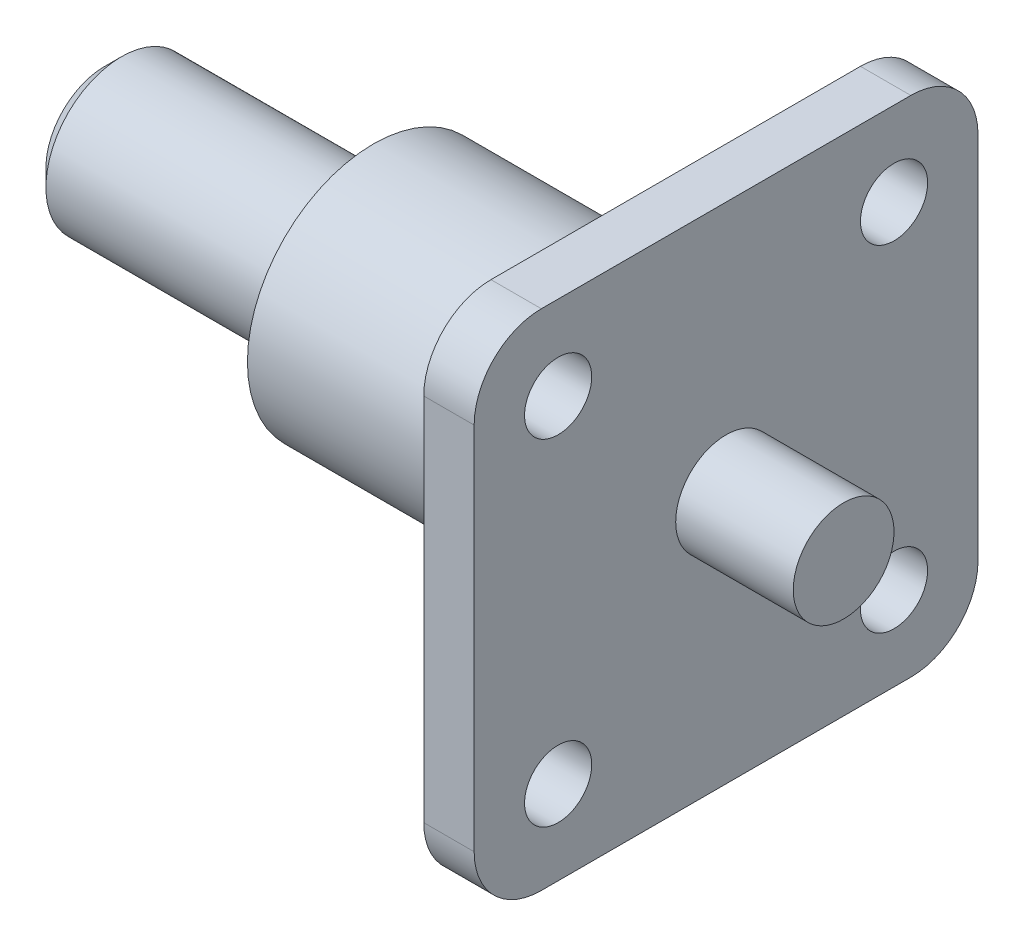
SolidWorks part; units mm, degrees
ref_plane "Alzado" through (0, 0, 0) normal (0, 0, 1) x (1, 0, 0)
ref_plane "Planta" through (0, 0, 0) normal (0, 1, 0) x (1, 0, 0)
ref_plane "Vista lateral" through (0, 0, 0) normal (1, 0, 0) x (0, 0, -1)
sketch "Croquis1" plane through (0, 0, 0) normal (0, 0, 1) x (1, 0, 0)
  line L0 (-18.3711, 0) -> (42.3295, 0) construction
  line L1 (-16, 0) -> (-16, 4.5)
  line L2 (-16, 4.5) -> (0, 4.5)
  line L3 (0, 4.5) -> (0, 7.5)
  line L4 (0, 7.5) -> (18, 7.5)
  line L5 (18, 7.5) -> (18, 0) construction
  line L6 (-16, 0) -> (28, 0)
  line L7 (18, 7.5) -> (18, 3)
  line L8 (18, 3) -> (28, 3)
  line L9 (28, 3) -> (28, 0)
  line L10 (0, 0) -> (0, 8.1876) construction
  point P9 (0, 6)
  point P10 (0, 8.1876)
  dimension "D1" = 9
  dimension "D2" = 15
  dimension "D3" = 16
  dimension "D4" = 18
  dimension "D5" = 6
  dimension "D6" = 10
revolve "Revolución1" add sketch "Croquis1" angle 360 about L0
fillet "Redondeo1" radius 1 1 edges at (0, 0, 4.5)
chamfer "Chaflán1" distance 1 angle 45 1 edges at (-16, 0, 4.5)
sketch "Croquis2" plane through (18, 0, 0) normal (1, 0, 0) x (0, 0, -1)
  line L1 (-11, -15) -> (11, -15)
  line L2 (-15, -11) -> (-15, 11)
  line L3 (-11, 15) -> (11, 15)
  line L4 (15, -11) -> (15, 11)
  line L5 (-15, -15) -> (15, 15) construction
  line L6 (-15, 15) -> (15, -15) construction
  line L7 (-10, -10) -> (10, -10) construction
  line L8 (-10, -10) -> (-10, 10) construction
  line L9 (-10, 10) -> (10, 10) construction
  line L10 (10, -10) -> (10, 10) construction
  line L11 (-10, -10) -> (10, 10) construction
  line L12 (-10, 10) -> (10, -10) construction
  circle A0 centre (-10, 10) radius 2
  circle A1 centre (10, 10) radius 2
  circle A2 centre (10, -10) radius 2
  circle A3 centre (-10, -10) radius 2
  arc A4 (-11, -15) -> (-15, -11) centre (-11, -11) cw
  arc A5 (11, -15) -> (15, -11) centre (11, -11) ccw
  arc A6 (11, 15) -> (15, 11) centre (11, 11) cw
  arc A7 (-15, 11) -> (-11, 15) centre (-11, 11) cw
  point P0 (0, 0)
  point P5 (0, 0)
  dimension "D4" = 4
  dimension "D5" = 4
  dimension "D1" = 30
  dimension "D2" = 30
  dimension "D3" = 20
extrude "Saliente-Extruir1" add sketch "Croquis2" along normal blind 3
